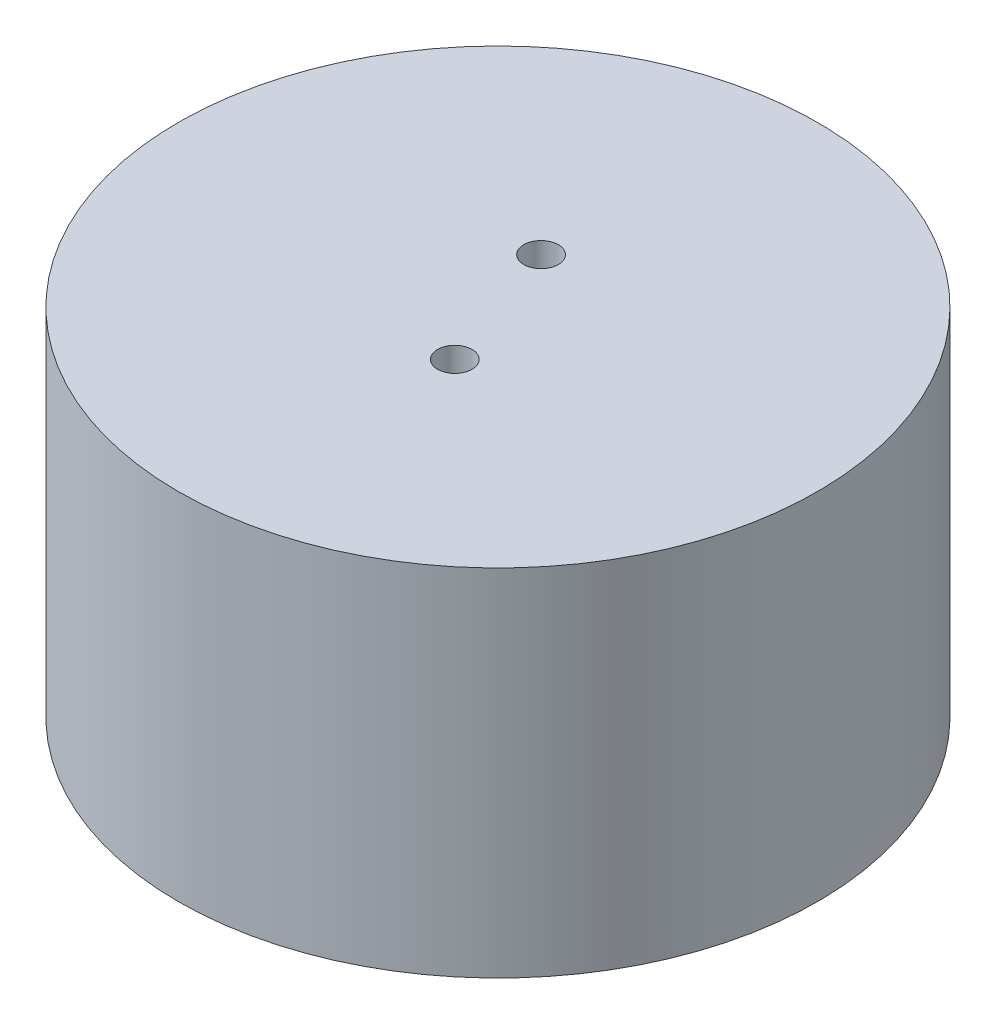
SolidWorks part; units mm, degrees
ref_plane "Front Plane" through (0, 0, 0) normal (0, 0, 1) x (1, 0, 0)
ref_plane "Top Plane" through (0, 0, 0) normal (0, 1, 0) x (1, 0, 0)
ref_plane "Right Plane" through (0, 0, 0) normal (1, 0, 0) x (0, 0, -1)
sketch "Sketch3" plane through (0, 0, 0) normal (0, 1, 0) x (1, 0, 0)
  circle A0 centre (0, 0) radius 26.5
  dimension "D1" = 53
sketch "Sketch4" plane through (0, 0, 0) normal (0, 1, 0) x (1, 0, 0)
  circle A0 centre (0, 0) radius 31.5
  circle A1 centre (0, 0) radius 26.5 construction
  dimension "D1" = 5
extrude "Boss-Extrude2" add sketch "Sketch4" along normal blind 35 contours A0
extrude "Cut-Extrude1" cut sketch "Sketch3" along normal blind 28 contours A0
sketch "Sketch5" plane through (0, 35, 0) normal (0, 1, 0) x (1, 0, 0)
  point P0 (0, 0)
sketch "Sketch7" plane through (0, 0, 0) normal (0, 0, 1) x (1, 0, 0)
  line L0 (0, 35) -> (0, 0)
hole_wizard "M3 Clearance Hole1" positions "Sketch9" profile "Sketch8" hole size "M3" standard "ANSI Metric"
sketch "Sketch9" plane through (0, 35, 0) normal (0, 1, 0) x (1, 0, 0)
  point P0 (-2.345, 6.5955)
  point P2 (2.345, -6.5955)
  dimension "D1" = 7
  dimension "D2" = 7
  dimension "D3" = 180
sketch "Sketch8" plane through (-2.345, 35, -6.5955) normal (1, 0, 0) x (0, 0, 1)
  line L0 (0, 0) -> (0, 51.0215)
  line L1 (0, 51.0215) -> (1.7, 50)
  line L2 (1.7, 50) -> (1.7, 0)
  line L5 (1.7, 0) -> (0, 0)
  line L10 (0, 51.0215) -> (-1.7, 50) construction
  line L11 (0, -6.35) -> (0, 107.95) construction
  dimension "Hole Dia." = 3.4
  dimension "Hole Depth" = 50
  dimension "Drill Angle" = 118
